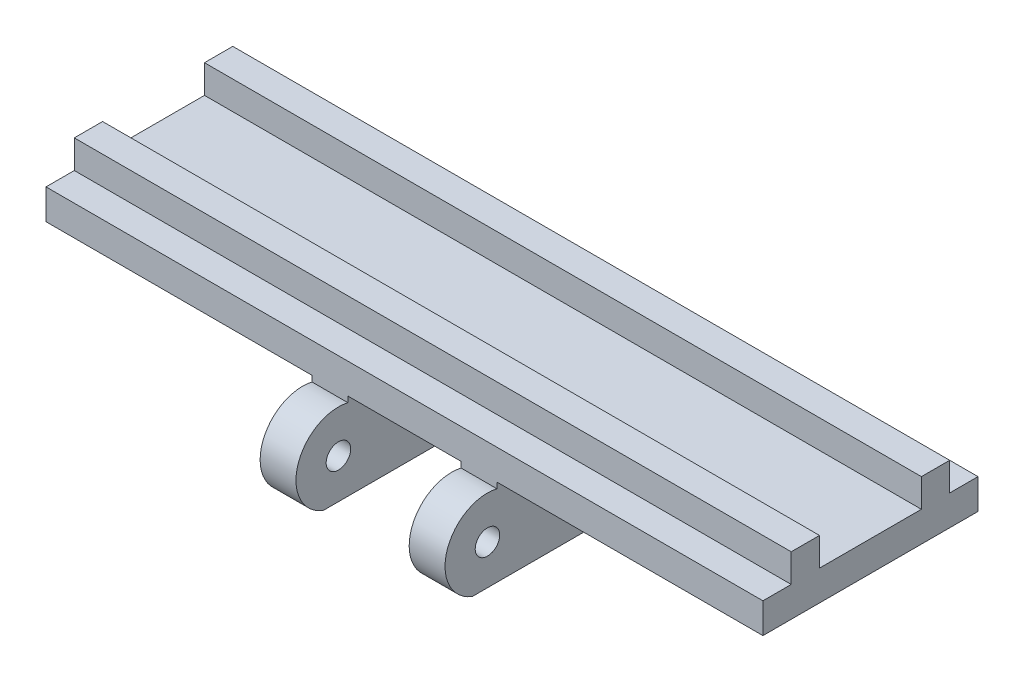
SolidWorks part; units mm, degrees
ref_plane "前视基准面" through (0, 0, 0) normal (0, 0, 1) x (1, 0, 0)
ref_plane "上视基准面" through (0, 0, 0) normal (0, 1, 0) x (1, 0, 0)
ref_plane "右视基准面" through (0, 0, 0) normal (1, 0, 0) x (0, 0, -1)
other "Configuration Table"
sketch "草图1" plane through (0, 0, 0) normal (0, 1, 0) x (1, 0, 0)
  line L0 (-3, 0) -> (3, 0) construction
  line L1 (-19, -5.7) -> (19, -5.7)
  line L2 (-19, -5.7) -> (-19, 5.7)
  line L3 (-19, 5.7) -> (19, 5.7)
  line L4 (19, -5.7) -> (19, 5.7)
  line L5 (-19, -5.7) -> (19, 5.7) construction
  line L6 (-19, 5.7) -> (19, -5.7) construction
  line L41 (-7, 7) -> (-3, 7)
  line L42 (-7, 7) -> (-7, -7)
  line L43 (-7, -7) -> (-3, -7)
  line L44 (-3, 7) -> (-3, -7)
  line L45 (3, 7) -> (7, 7)
  line L46 (3, 7) -> (3, -7)
  line L47 (3, -7) -> (7, -7)
  line L48 (7, 7) -> (7, -7)
  point P0 (0, 0)
  point P6 (0, 0)
  point P7 (0, 0)
  point P12 (0, 0)
  dimension "D1" = 38
  dimension "D2" = 11.4
  dimension "D3" = 6
  dimension "D4" = 4
  dimension "D5" = 14
extrude "凸台-拉伸1" add sketch "草图1" along normal blind 1.6 contours L2 L3 L4 L1
extrude "凸台-拉伸2" add sketch "草图1<4>" against normal blind 5 contours L48 L47 L46 L45 | L44 L43 L42 L41
sketch "草图1<4>" plane through (0, 0, 0) normal (0, 1, 0) x (1, 0, 0) same geometry as "草图1"
sketch "草图2" plane through (0, 0, 0) normal (0, 1, 0) x (1, 0, 0)
  line L1 (-5, 7) -> (5, 7)
  line L2 (-5, 7) -> (-5, 5.7)
  line L3 (-5, 5.7) -> (5, 5.7)
  line L4 (5, 7) -> (5, 5.7)
  line L5 (-7, 7) -> (-3, 7) construction
  line L6 (-19, 5.7) -> (19, 5.7) construction
  line L7 (3, 7) -> (7, 7) construction
  line L9 (-5, -7) -> (-7, -7)
  line L10 (-5, -7) -> (-5, -5.7)
  line L11 (-5, -5.7) -> (-7, -5.7)
  line L12 (-7, -7) -> (-7, -5.7)
  line L13 (-7, -7) -> (-3, -7) construction
  line L14 (-19, -5.7) -> (19, -5.7) construction
  line L17 (-7, -5.7) -> (-7, -7) construction
  line L18 (5, -7) -> (7, -7)
  line L19 (5, -7) -> (5, -5.7)
  line L20 (5, -5.7) -> (7, -5.7)
  line L21 (7, -7) -> (7, -5.7)
  line L22 (3, -7) -> (7, -7) construction
  line L23 (7, -5.7) -> (7, -7) construction
  line L25 (-5, 7) -> (-5.1, 7)
  line L26 (-5, 7) -> (-5, 5.7)
  line L27 (-5, -5.7) -> (-4.9, -5.7)
  line L28 (-5, -5.7) -> (-5, -7)
  line L29 (-5, -7) -> (-4.9, -7)
  line L30 (-4.9, -5.7) -> (-4.9, -7)
  line L31 (5, -5.7) -> (4.9, -5.7)
  line L32 (5, -5.7) -> (5, -7)
  line L33 (5, -7) -> (4.9, -7)
  line L34 (4.9, -5.7) -> (4.9, -7)
  line L35 (-5, 5.7) -> (-5.1, 5.7)
  line L36 (-5.1, 7) -> (-5.1, 5.7)
  line L37 (5, 7) -> (5.1, 7)
  line L38 (5, 7) -> (5, 5.7)
  line L39 (5, 5.7) -> (5.1, 5.7)
  line L40 (5.1, 7) -> (5.1, 5.7)
  dimension "D1" = 0.1
  dimension "D2" = 0.1
  dimension "D3" = 0.1
  dimension "D4" = 0.1
extrude "切除-拉伸1" cut sketch "草图2" against normal through all contours L25 L36 L35 L2 | L4 L1 L2 L3 | L40 L37 L4 L39 | L12 L9 L10 L11 | L30 L27 L10 L29 | L31 L34 L33 L19 | L18 L21 L20 L19 region at (0, 0, -6.35) region at (-5.05, 0, -6.35) region at (5.05, 0, -6.35) region at (-6, 0, 6.35) region at (-4.95, 0, 6.35) region at (6, 0, 6.35) region at (4.95, 0, 6.35)
sketch "草图3" plane through (0, 0, 0) normal (1, 0, 0) x (0, 0, -1)
  line L1 (-6.2, -2.5) -> (6.2, -2.5)
  circle A0 centre (-6.2, -2.5) radius 0.65
  circle A1 centre (6.2, -2.5) radius 0.55
  point P2 (0, -2.5)
  dimension "D2" = 1.3
  dimension "D3" = 1.1
  dimension "D1" = 2.5
  dimension "D4" = 12.4
sketch "草图4" plane through (0, 0, 0) normal (1, 0, 0) x (0, 0, -1)
  line L0 (-5.7, 0) -> (5.7, 0) construction
  line L6 (-5.7, 0) -> (-3.7, 0)
  line L7 (-5.7, 0) -> (-5.7, -5)
  line L8 (-5.7, -5) -> (-3.7, -5)
  line L9 (-3.7, 0) -> (-3.7, -5)
  line L10 (5.7, 0) -> (8.45, 0)
  line L11 (5.7, 0) -> (5.7, -2.5)
  line L12 (5.7, -2.5) -> (8.45, -2.5)
  line L13 (8.45, 0) -> (8.45, -2.5)
  line L14 (5.7, -5) -> (8.45, -5)
  line L15 (5.7, -5) -> (5.7, -2.5)
  line L16 (5.7, -2.5) -> (8.45, -2.5)
  line L17 (8.45, -5) -> (8.45, -2.5)
  circle A0 centre (-6.2, -2.5) radius 2.5
  circle A1 centre (6.2, -2.5) radius 2.25
  dimension "D1" = 4.5
extrude "切除-拉伸2" cut sketch "草图4" against normal up to surface (-4.9 mm away) from surface contours A0 L8 L9 | A0 region at (0, -4.4382, 4.2486) up to face at (4.9, -2.5, 6.35) starting at face at (7, -2, -1.66)
extrude "切除-拉伸3" cut sketch "草图4<3>" along normal up to surface (-4.9 mm away) from surface contours A0 L8 L9 | A0 region at (0, -4.4382, 4.2486) up to face at (-4.9, -2.5, 6.35) starting at face at (-7, -2, -1.66)
sketch "草图4<3>" plane through (0, 0, 0) normal (1, 0, 0) x (0, 0, -1) same geometry as "草图4"
extrude "切除-拉伸6" cut sketch "草图4<5>" against normal through all both and the other way through all contours A1 L13 L10 L11 | A1 L15 L14 L17 region at (0, -0.5081, -7.6) region at (0, -4.4919, -7.6)
sketch "草图4<5>" plane through (0, 0, 0) normal (1, 0, 0) x (0, 0, -1) same geometry as "草图4"
extrude "凸台-拉伸3" add sketch "草图4<6>" along normal up to surface (7 mm away) from surface contours L12 A1 L11 | L14 A1 L12 L15 region at (0, -1.5098, -6.8911) region at (0, -3.4902, -6.8911) up to face at (7, -2.2194, -1.845) starting at face at (5.1, -2.5, -6.3534)
sketch "草图4<6>" plane through (0, 0, 0) normal (1, 0, 0) x (0, 0, -1) same geometry as "草图4"
extrude "凸台-拉伸4" add sketch "草图4<7>" against normal up to surface (1.9 mm away) from surface contours L12 A1 L11 | L14 A1 L12 L15 region at (0, -1.5098, -6.8911) region at (0, -3.4902, -6.8911) up to face at (-7, -2.2194, -1.845) starting at face at (-5.1, -2.5, -6.3534)
sketch "草图4<7>" plane through (0, 0, 0) normal (1, 0, 0) x (0, 0, -1) same geometry as "草图4"
extrude "切除-拉伸7" cut sketch "草图3" against normal through all both and the other way through all contours A0 | A1
sketch "草图5" plane through (0, 0, 0) normal (1, 0, 0) x (0, 0, -1)
  line L0 (-5.7, 0) -> (5.7, 0) construction
  line L6 (6.2, -2.5) -> (3.7, -2.5)
  line L7 (6.2, -2.5) -> (6.2, -5)
  line L8 (6.2, -5) -> (3.7, -5)
  line L9 (3.7, -2.5) -> (3.7, -5)
  circle A0 centre (6.2, -2.5) radius 2.5
extrude "切除-拉伸8" cut sketch "草图5" along normal up to surface (5.1 mm away) contours A0 L9 L8 | A0 region at (0, -4.4416, -4.2584) up to face at (5.1, -2.5, -6.65)
extrude "切除-拉伸9" cut sketch "草图5<2>" against normal up to surface (5.1 mm away) contours A0 L9 L8 | A0 region at (0, -4.4416, -4.2584) up to face at (-5.1, -2.5, -6.65)
sketch "草图5<2>" plane through (0, 0, 0) normal (1, 0, 0) x (0, 0, -1) same geometry as "草图5"
sketch "草图7" plane through (0, 0, 0) normal (1, 0, 0) x (0, 0, -1)
  line L0 (-3.7, -5) -> (-7, -5) construction
  line L1 (-5.7, 0) -> (-8.45, 0)
  line L2 (-5.7, 0) -> (-5.7, -2.5)
  line L3 (-5.7, -2.5) -> (-8.45, -2.5)
  line L4 (-8.45, 0) -> (-8.45, -2.5)
  line L5 (-5.7, -2.5) -> (-8.45, -2.5)
  line L6 (-5.7, -2.5) -> (-5.7, -5)
  line L7 (-5.7, -5) -> (-8.45, -5)
  line L8 (-8.45, -2.5) -> (-8.45, -5)
  circle A0 centre (-6.2, -2.5) radius 2.25
  dimension "D1" = 4.5
extrude "切除-拉伸10" cut sketch "草图7" against normal through all both and the other way through all contours A0 L2 L1 L4 region at (0, -0.5081, 7.6)
extrude "凸台-拉伸5" add sketch "草图7<4>" along normal up to surface (1.9 mm away) from surface contours L2 A0 L3 | L3 A0 L7 L6 region at (0, -1.5098, 6.8911) region at (0, -3.4902, 6.8911) up to face at (4.9, -2.5, 6.85) starting at face at (3, -2.5, 6.85)
sketch "草图7<4>" plane through (0, 0, 0) normal (1, 0, 0) x (0, 0, -1) same geometry as "草图7"
extrude "凸台-拉伸6" add sketch "草图7<5>" against normal up to surface (1.9 mm away) from surface contours L2 A0 L3 | L3 A0 L7 L6 region at (0, -1.5098, 6.8911) region at (0, -3.4902, 6.8911) up to face at (-4.9, -2.5, 6.85) starting at face at (-3, -2.5, 6.85)
sketch "草图7<5>" plane through (0, 0, 0) normal (1, 0, 0) x (0, 0, -1) same geometry as "草图7"
extrude "切除-拉伸11" cut sketch "草图3<3>" against normal through all both and the other way through all contours A0 | A1
sketch "草图3<3>" plane through (0, 0, 0) normal (1, 0, 0) x (0, 0, -1) same geometry as "草图3"
sketch "草图9" plane through (0, 0, 0) normal (1, 0, 0) x (0, 0, -1)
  line L0 (5.7, -5) -> (-3.7, -5) construction
  line L1 (-7, -4.603) -> (8.45, -4.603)
  line L2 (-7, -4.603) -> (-7, -5)
  line L3 (-7, -5) -> (8.45, -5)
  line L4 (8.45, -4.603) -> (8.45, -5)
  arc A0 (5.7, -4.6937) -> (5.7, -0.3063) centre (6.2, -2.5) ccw construction
extrude "切除-拉伸12" cut sketch "草图9" against normal through all both and the other way through all contours L3 L4 L1 L2
sketch "草图10" plane through (0, 1.6, 0) normal (0, 1, 0) x (1, 0, 0)
  line L0 (19, -5.7) -> (19, 5.7) construction
  line L1 (-19, 2.7) -> (19, 2.7)
  line L2 (-19, 2.7) -> (-19, 4.2)
  line L3 (-19, 4.2) -> (19, 4.2)
  line L4 (19, 2.7) -> (19, 4.2)
  line L5 (-19, -4.2) -> (19, -4.2)
  line L6 (-19, -4.2) -> (-19, -2.7)
  line L7 (-19, -2.7) -> (19, -2.7)
  line L8 (19, -4.2) -> (19, -2.7)
  line L9 (-19, -5.7) -> (-19, 5.7) construction
  line L10 (0, 2.7) -> (0, -2.7)
  line L12 (-19, 5.7) -> (19, 5.7) construction
  circle A0 centre (0, 0) radius 2.5
  circle A1 centre (-7, 0) radius 2.5
  circle A2 centre (7, 0) radius 2.5
  circle A3 centre (14, 0) radius 2.5
  circle A4 centre (-14, 0) radius 2.5
  point P0 (0, 0)
  dimension "D3" = 5
  dimension "D1" = 1.5
  dimension "D2" = 1.5
  dimension "D4" = 7
  dimension "D5" = 7
  dimension "D6" = 7
  dimension "D7" = 7
extrude "凸台-拉伸7" add sketch "草图10" along normal blind 1.5 contours L1 L4 L3 L2 | L5 L8 L7 L6
fillet "圆角1" radius 1 4 edges at (4.05, -4.603, -3.7) (-4.05, -4.603, -3.7) (-5.95, -4.603, 3.7) (5.95, -4.603, 3.7)
sketch "草图11" plane through (0, 0, 0) normal (1, 0, 0) x (0, 0, -1)
  line L0 (7, -4.603) -> (-2.7, -4.603) construction
  line L1 (-5.7, 0) -> (-1, 0)
  line L2 (-5.7, 0) -> (-5.7, -4.603)
  line L3 (-5.7, -4.603) -> (-1, -4.603)
  line L4 (-1, 0) -> (-1, -4.603)
  line L6 (5.7, 0) -> (1, 0)
  line L7 (5.7, 0) -> (5.7, -4.603)
  line L8 (5.7, -4.603) -> (1, -4.603)
  line L9 (1, 0) -> (1, -4.603)
  dimension "D1" = 1
  dimension "D2" = 1
extrude "切除-拉伸13" cut sketch "草图11" against normal through all from surface contours L4 L3 L2 L1 starting at face at (-4.9, -2.5, 6.85)
extrude "切除-拉伸14" cut sketch "草图11<2>" along normal through all from surface contours L4 L3 L2 L1 starting at face at (4.9, -2.5, 6.85)
sketch "草图11<2>" plane through (0, 0, 0) normal (1, 0, 0) x (0, 0, -1) same geometry as "草图11"
extrude "切除-拉伸15" cut sketch "草图11<4>" against normal up to surface (10.2 mm away) from surface contours L9 L8 L7 L6 up to face at (-5.1, -2.5, -5.65) starting at face at (5.1, -2.5, -5.65)
sketch "草图11<4>" plane through (0, 0, 0) normal (1, 0, 0) x (0, 0, -1) same geometry as "草图11"
